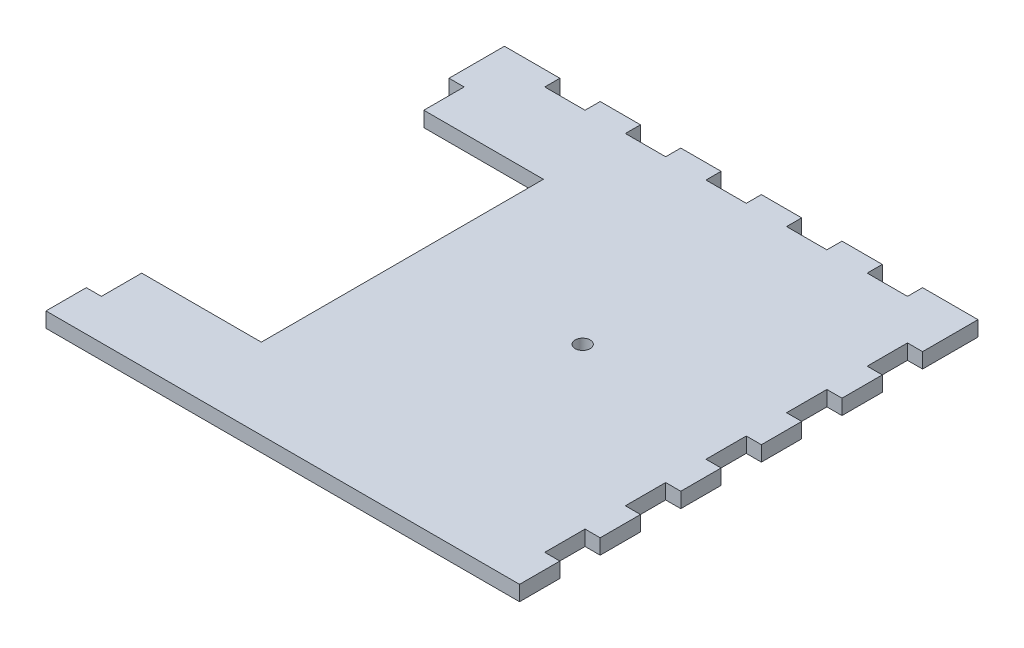
SolidWorks part; units mm, degrees
ref_plane "Front Plane" through (0, 0, 0) normal (0, 0, 1) x (1, 0, 0)
ref_plane "Top Plane" through (0, 0, 0) normal (0, 1, 0) x (1, 0, 0)
ref_plane "Right Plane" through (0, 0, 0) normal (1, 0, 0) x (0, 0, -1)
sketch "Sketch1" plane through (0, 0, 0) normal (0, 1, 0) x (1, 0, 0)
  line L1 (-139.7, -139.7) -> (139.7, -139.7)
  line L2 (-139.7, -139.7) -> (-139.7, 139.7)
  line L3 (-139.7, 139.7) -> (139.7, 139.7)
  line L4 (139.7, -139.7) -> (139.7, 139.7)
  line L5 (-139.7, -139.7) -> (139.7, 139.7) construction
  line L6 (-139.7, 139.7) -> (139.7, -139.7) construction
  point P0 (0, 0)
  dimension "D1" = 279.4
  dimension "D2" = 279.4
extrude "Boss-Extrude1" add sketch "Sketch1" along normal blind 9.525
sketch "Sketch2" plane through (139.7, 0, 0) normal (1, 0, 0) x (0, 0, -1)
  line L0 (-139.7, 9.525) -> (139.7, 9.525) construction
  line L1 (-139.7, 0) -> (-114.3, 0)
  line L2 (-139.7, 0) -> (-139.7, 9.525)
  line L3 (-139.7, 9.525) -> (-114.3, 9.525)
  line L4 (-114.3, 0) -> (-114.3, 9.525)
  dimension "D1" = 25.4
extrude "Boss-Extrude2" add sketch "Sketch2" along normal blind 9.525
pattern_linear "LPattern1" count 6 spacing 50.8 along (0, 0, -1) of "Boss-Extrude2"
mirror "Mirror1" about plane through (0, 0, 0) normal (1, 0, 0) of "LPattern1"
sketch "Sketch3" plane through (0, 0, -139.7) normal (0, 0, -1) x (-1, 0, 0)
  line L0 (-149.225, 9.525) -> (149.225, 9.525) construction
  line L1 (-139.7, 9.525) -> (-114.3, 9.525)
  line L2 (-139.7, 9.525) -> (-139.7, 0)
  line L3 (-139.7, 0) -> (-114.3, 0)
  line L4 (-114.3, 9.525) -> (-114.3, 0)
  line L5 (-149.225, 0) -> (149.225, 0) construction
  line L6 (-149.225, 0) -> (-149.225, 9.525) construction
  dimension "D1" = 9.525
  dimension "D2" = 25.4
extrude "Boss-Extrude3" add sketch "Sketch3" along normal blind 9.525
pattern_linear "LPattern2" count 6 spacing 50.8 along (-1, 0, 0) of "Boss-Extrude3"
sketch "Sketch5" plane through (0, 0, -139.7) normal (0, 0, -1) x (-1, 0, 0)
  line L0 (158.9088, 0) -> (-158.9088, 0) construction
  line L1 (-149.225, 9.525) -> (-139.7, 9.525)
  line L2 (-149.225, 9.525) -> (-149.225, 0)
  line L3 (-149.225, 0) -> (-139.7, 0)
  line L4 (-139.7, 9.525) -> (-139.7, 0)
  line L5 (-139.7, 9.525) -> (-139.7, 0) construction
extrude "Boss-Extrude4" add sketch "Sketch5" along normal blind 9.525
mirror "Mirror2" about plane through (0, 0, 0) normal (1, 0, 0) of "Boss-Extrude4"
sketch "Sketch6" plane through (0, 9.525, 0) normal (0, 1, 0) x (1, 0, 0)
  line L0 (63.5, 139.7) -> (38.1, 139.7) construction
  line L1 (139.7, -12.7) -> (139.7, 12.7) construction
  circle A0 centre (38.1, 11.176) radius 4.7625
  dimension "D1" = 128.524
  dimension "D3" = 9.525
  dimension "D2" = 101.6
extrude "Cut-Extrude1" cut sketch "Sketch6" against normal through all
sketch "Sketch8" plane through (0, 9.525, 0) normal (0, 1, 0) x (1, 0, 0)
  line L1 (-149.225, 88.9) -> (-64.3339, 88.9)
  line L2 (-149.225, 88.9) -> (-149.225, -88.9)
  line L3 (-149.225, -88.9) -> (-64.3339, -88.9)
  line L4 (-64.3339, 88.9) -> (-64.3339, -88.9)
  dimension "D1" = 177.8
extrude "Cut-Extrude3" cut sketch "Sketch8" against normal through all
sketch "Sketch7" plane through (0, 9.525, 0) normal (0, 1, 0) x (1, 0, 0)
  line L0 (-139.7, 63.5) -> (-139.7, 38.1) construction
  line L1 (-139.7, 114.3) -> (-139.7, 88.9) construction
  line L2 (-88.9, 139.7) -> (-114.3, 139.7) construction
  circle A0 centre (-101.6, 65.278) radius 5.08
  circle A1 centre (-101.6, 27.686) radius 5.08
  dimension "D1" = 10.16
  dimension "D2" = 10.16
  dimension "D3" = 38.1
  dimension "D4" = 38.1
  dimension "D5" = 37.592
  dimension "D6" = 74.422
extrude "Cut-Extrude2" cut sketch "Sketch7" against normal through all rebuild error yes
